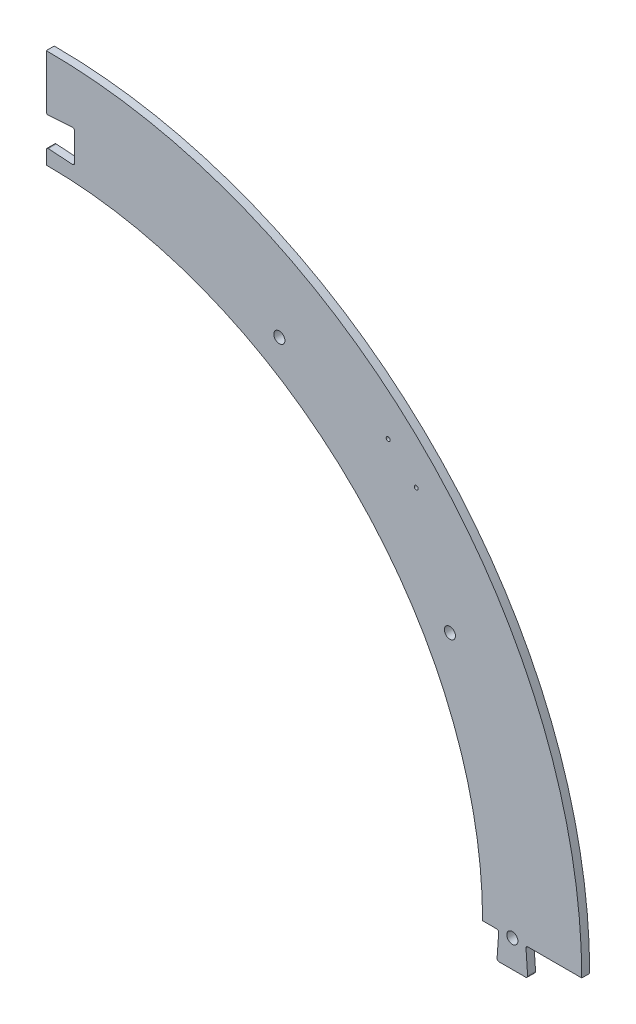
SolidWorks part; units mm, degrees
ref_plane "Front Plane" through (0, 0, 0) normal (0, 0, 1) x (1, 0, 0)
ref_plane "Top Plane" through (0, 0, 0) normal (0, 1, 0) x (1, 0, 0)
ref_plane "Right Plane" through (0, 0, 0) normal (1, 0, 0) x (0, 0, -1)
sketch "Sketch1" plane through (0, 0, 0) normal (0, 0, 1) x (1, 0, 0)
  circle A0 centre (0, 0) radius 125
  dimension "D1" = 250
sketch "Sketch2" plane through (0, 0, 0) normal (0, 0, 1) x (1, 0, 0)
  line L0 (0, 135) -> (0, 110)
  line L1 (110, 0) -> (135, 0)
  arc A0 (0, 135) -> (135, 0) centre (0, 0) cw
  arc A1 (0, 110) -> (110, 0) centre (0, 0) cw
  dimension "D1" = 135
  dimension "D2" = 110
extrude "Boss-Extrude1" add sketch "Sketch2" along normal blind 2
sketch "Sketch3" plane through (0, 0, 0) normal (0, 0, -1) x (-1, 0, 0)
  line L0 (-110, 0) -> (-135, 0) construction
  line L1 (0, 135) -> (0, 110) construction
  line L2 (0, 125.8) -> (0, 125)
  line L3 (-125.8, 0) -> (-125, 0)
  arc A0 (-125, 0) -> (0, 125) centre (0, 0) cw
  circle A1 centre (0, 0) radius 125 construction
  arc A2 (-125.8, 0) -> (0, 125.8) centre (0, 0) cw
  dimension "D1" = 0.8
extrude "Boss-Extrude2" add sketch "Sketch3" along normal blind 2
sketch "Sketch5" plane through (0, 0, 0) normal (0, 0, 1) x (1, 0, 0)
  line L0 (114, 0) -> (113.5, -7)
  line L1 (110, 0) -> (135, 0) construction
  line L2 (113.5, -7) -> (121.5, -7)
  line L3 (121.5, -7) -> (121, 0)
  line L4 (121, 0) -> (114, 0)
  line L5 (110, 0) -> (125, 0) construction
  line L6 (0, 121) -> (0, 114)
  line L7 (0, 114) -> (7, 113.5)
  line L8 (7, 113.5) -> (7, 121.5)
  line L9 (7, 121.5) -> (0, 121)
  line L10 (0, 135) -> (0, 110) construction
  point P10 (117.5, 0)
  point P12 (-15.8536, 117.8203)
  point P13 (0, 0)
  point P17 (0, 0)
  dimension "D1" = 8
  dimension "D2" = 7
  dimension "D3" = 7
  dimension "D4" = 2
sketch "Sketch7" plane through (0, 0, 0) normal (0, 0, 1) x (1, 0, 0)
  line L14 (121, 0) -> (114, 0) construction
  line L15 (114.1003, 0) -> (120.8997, 0)
  line L16 (113.6074, -6.9) -> (121.3926, -6.9)
  line L17 (114.0997, -0.0071) -> (113.6074, -6.9)
  line L18 (121.3926, -6.9) -> (120.9003, -0.0071)
  line L19 (113.6074, -6.9) -> (121.3926, -6.9)
  line L20 (114.1003, 0) -> (113.6074, -6.9)
  line L21 (121.3926, -6.9) -> (120.8997, 0)
  dimension "D1" = 0.1
extrude "Boss-Extrude3" add sketch "Sketch7" along normal up to surface (2 mm away) up to face at (73.9353, 73.9353, 2)
sketch "Sketch8" plane through (0, 0, 2) normal (0, 0, 1) x (1, 0, 0)
  line L9 (-0.0071, 121.0997) -> (-0.0071, 113.9003)
  line L12 (-0.0071, 113.9003) -> (7.1, 113.3926)
  line L13 (7.1, 113.3926) -> (7.1, 121.6074)
  line L14 (7.1, 121.6074) -> (-0.0071, 121.0997)
  line L15 (-0.0071, 113.9003) -> (7.1, 113.3926)
  line L16 (7.1, 113.3926) -> (7.1, 121.6074)
  line L17 (7.1, 121.6074) -> (-0.0071, 121.0997)
  dimension "D1" = 0.1
extrude "Cut-Extrude1" cut sketch "Sketch8" against normal up to next
fillet "Fillet1" radius 0.5 8 edges at (0, 113.8997, 1) (7.1, 113.3926, 1) (7.1, 121.6074, 1) (0, 121.1003, 1) (121.3926, -6.9, 1) (113.6074, -6.9, 1) (114.1003, 0, 1) (120.8997, 0, 1)
sketch "Sketch4" plane through (0, 0, 0) normal (0, 0, 1) x (1, 0, 0)
  line L0 (0, 135) -> (0, 121.6372) construction
  line L1 (110, 0) -> (113.5633, 0) construction
  line L2 (0, 125) -> (0, 110) construction
  line L3 (0, 0) -> (58.75, 101.758) construction
  line L4 (0, 0) -> (101.758, 58.75) construction
  line L5 (0, 0) -> (117.5, 0) construction
  arc A0 (0, 117.5) -> (117.5, 0) centre (0, 0) cw construction
  arc A1 (110, 0) -> (0, 110) centre (0, 0) ccw construction
  circle A2 centre (58.75, 101.758) radius 1.4
  circle A3 centre (101.758, 58.75) radius 1.4
  circle A4 centre (117.5, 0) radius 1.4
  point P16 (0, 117.5)
  dimension "D1" = 2.8
  dimension "D2" = 30
  dimension "D3" = 30
extrude "Cut-Extrude3" cut sketch "Sketch4" along normal up to next
sketch "Sketch9" plane through (0, 0, 0) normal (0, 0, -1) x (-1, 0, 0)
  line L0 (0, 135) -> (0, 125.8) construction
  line L1 (-125.8, 0) -> (-135, 0) construction
  line L2 (0, 0) -> (-89.8026, 89.8026) construction
  arc A0 (-127, 0) -> (0, 127) centre (0, 0) cw construction
  circle A1 centre (-93.2685, 86.1974) radius 0.5
  circle A2 centre (-86.1974, 93.2685) radius 0.5
  point P12 (-92.9786, 86.51)
  dimension "D1" = 1
  dimension "D3" = 127
  dimension "D2" = 10
extrude "Cut-Extrude4" cut sketch "Sketch9" against normal up to next
